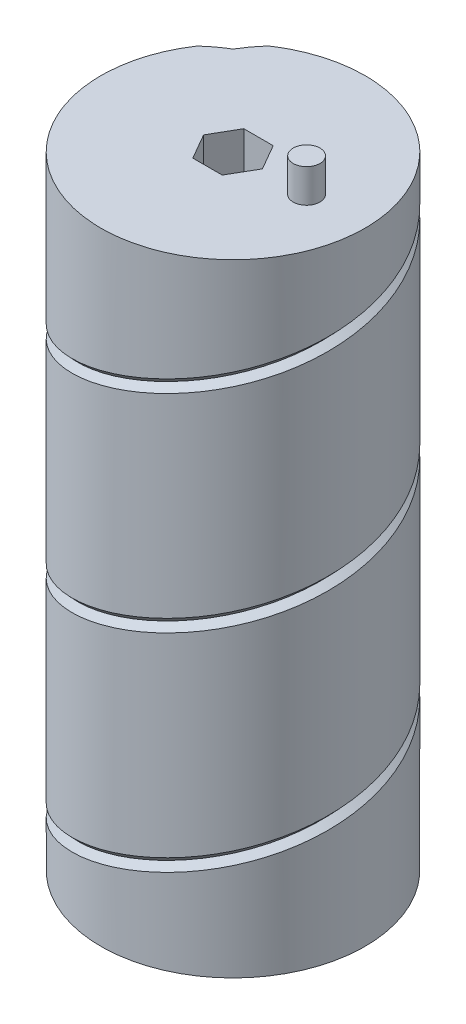
SolidWorks part; units mm, degrees
ref_plane "Front Plane" through (0, 0, 0) normal (0, 0, 1) x (1, 0, 0)
ref_plane "Top Plane" through (0, 0, 0) normal (0, 1, 0) x (1, 0, 0)
ref_plane "Right Plane" through (0, 0, 0) normal (1, 0, 0) x (0, 0, -1)
sketch "Sketch1" plane through (0, 0, 0) normal (0, 1, 0) x (1, 0, 0)
  line L0 (-19.75, 0) -> (19.75, 0) construction
  circle A0 centre (0, 0) radius 19.75
  dimension "D1" = 39.5
curve "Helix - Antenna Guide" pitch 31 height 93 radius 19.75 centre (0, 0, 0) axis (0, 1, 0) start towards (0, 0, 1)
extrude "Extrude - Main Body" add sketch "Sketch1<2>" along normal blind 93
sketch "Sketch1<2>" plane through (0, 0, 0) normal (0, 1, 0) x (1, 0, 0) same geometry as "Sketch1"
ref_point "Point2"
ref_point "Point1"
ref_plane "Plane1" through (-13.9654, 0, -13.9654) normal (-0.686, 0.2424, 0.686) x (-0.7276, -0.2285, -0.6468)
sketch "Sketch15" plane through (-13.9654, 0, -13.9654) normal (-0.686, 0.2424, 0.686) x (-0.7276, -0.2285, -0.6468)
  line L4 (0, 0) -> (0.2165, 0.8934)
  line L5 (0.2165, 0.8934) -> (-0.8934, 0.2165)
  line L8 (0, 0) -> (-0.2165, -0.8934)
  line L9 (-0.2165, -0.8934) -> (-0.8934, 0.2165)
  point P7 (-0.5549, -0.3384)
  dimension "D1" = 0.65
  dimension "D2" = 90
sweep "Cut - Antenna Wire Guide" cut profiles "Sketch15" path "Helix - Antenna Guide" align with end faces yes
sketch "Sketch23" plane through (0, 0, 0) normal (0, -1, 0) x (1, 0, 0)
  line L0 (-13.3154, -13.3154) -> (-8.3849, -14.1466)
  line L1 (-9.335, -17.4046) -> (-10.0329, -12.4535)
  arc A0 (-11.0473, -16.3713) -> (-16.3713, -11.0473) centre (0, 0) ccw construction
  arc A1 (-10.0329, -12.4535) -> (-8.3849, -14.1466) centre (-8.0525, -12.1744) cw
  arc A2 (-9.335, -17.4046) -> (-13.3154, -13.3154) centre (-14.1184, -18.0788) cw
  dimension "D2" = 2
  dimension "D1" = 2
  dimension "D3" = 5
  dimension "D4" = 5
ref_plane "Plane - Anchor Loop Exit" through (-9.335, 0, -17.4046) normal (-0.1396, 0, 0.9902) x (0.9902, 0, 0.1396)
ref_plane "Plane - Anchor Loop Peg" through (-10.0329, 0, -12.4535) normal (-0.1396, 0, 0.9902) x (0.9902, 0, 0.1396)
sketch "Sketch28" plane through (0, 93, 0) normal (0, 1, 0) x (1, 0, 0)
  circle A0 centre (11, 0) radius 2
  point P0 (0, 0)
  dimension "D1" = 4
  dimension "D2" = 11
extrude "Extruded Peg" add sketch "Sketch28" along normal blind 5
hole_wizard "Hole for Threaded Rod" positions "Sketch29" profile "Sketch30" hole size "#8" standard "ANSI Inch" end condition through all
sketch "Sketch29" plane through (0, 93, 0) normal (0, 1, 0) x (1, 0, 0)
  point P0 (0, 0)
sketch "Sketch30" plane through (0, 93, 0) normal (1, 0, 0) x (0, 0, 1)
  line L0 (0, 0) -> (0, 94.4693)
  line L1 (0, 94.4693) -> (2.2479, 94.4693)
  line L2 (2.2479, 94.4693) -> (2.2479, 0)
  line L5 (2.2479, 0) -> (0, 0)
  line L11 (0, -6.35) -> (0, 107.95) construction
  dimension "Thru Hole Dia." = 4.4958
  dimension "Thru Hole Depth" = 94.4693
sketch "Sketch31" plane through (0, 0, 0) normal (0, -1, 0) x (1, 0, 0)
  circle A0 centre (11, 0) radius 2.25
  dimension "D1" = 4.5
  dimension "D2" = 11
extrude "Cut Peg" cut sketch "Sketch31" against normal blind 5.5
sketch "Sketch32" plane through (0, 93, 0) normal (0, 1, 0) x (1, 0, 0)
  line L1 (-2.1997, -3.81) -> (2.1997, -3.81)
  line L2 (2.1997, -3.81) -> (4.3994, 0)
  line L3 (4.3994, 0) -> (2.1997, 3.81)
  line L4 (2.1997, 3.81) -> (-2.1997, 3.81)
  line L5 (-2.1997, 3.81) -> (-4.3994, 0)
  line L6 (-4.3994, 0) -> (-2.1997, -3.81)
  circle A1 centre (0, 0) radius 3.81 construction
  point P1 (2.6043, 2.5804)
  point P11 (0, 0)
  dimension "D1" = 7.62
extrude "Cut-Extrude1" cut sketch "Sketch32" against normal blind 26.67
equation "\"pegD\"=10"
equation "\"pegHoleD\"=0.5"
equation "\"pegHoleOffset\"=0.5"
